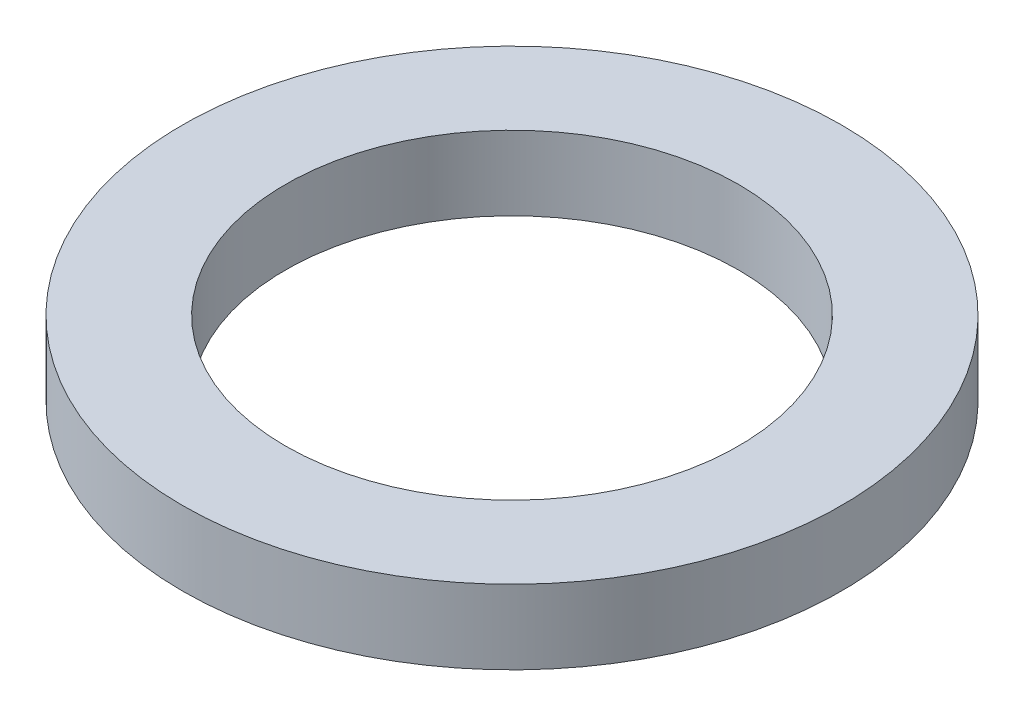
SolidWorks part; units mm, degrees
ref_plane "Front Plane" through (0, 0, 0) normal (0, 0, 1) x (1, 0, 0)
ref_plane "Top Plane" through (0, 0, 0) normal (0, 1, 0) x (1, 0, 0)
ref_plane "Right Plane" through (0, 0, 0) normal (1, 0, 0) x (0, 0, -1)
sketch "Sketch1" plane through (0, 0, 0) normal (0, 1, 0) x (1, 0, 0)
  circle A0 centre (0, 0) radius 40
  dimension "FLANGE_OD" = 80
extrude "Boss-Extrude1" add sketch "Sketch1" along normal blind 9
sketch "Sketch2" plane through (0, 0, 0) normal (0, 1, 0) x (1, 0, 0)
  circle A0 centre (0, 0) radius 27.5
  dimension "BORE_D" = 55
extrude "Cut-Extrude1" cut sketch "Sketch2" along normal through all
sketch "Sketch3" plane through (0, 9, 0) normal (0, 1, 0) x (1, 0, 0)
  circle A0 centre (0, 0) radius 15.558 construction
  circle A1 centre (-15.558, 0) radius 2.2226
  dimension "BOLT_D" = 4.4452
  dimension "BOLT_PCD" = 31.1159
extrude "Cut-Extrude2" cut sketch "Sketch3" against normal blind 8.4004 rebuild error yes
pattern_circular "CirPattern1" count 6 over 360 rebuild error yes
